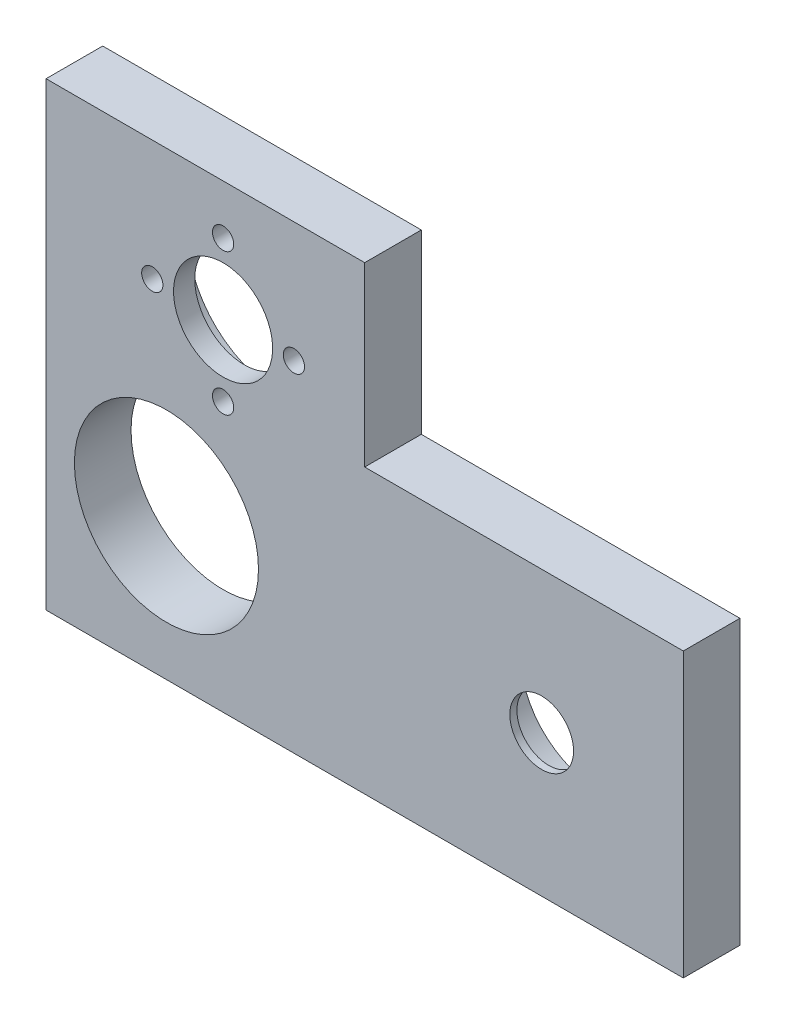
SolidWorks part; units mm, degrees
ref_plane "Front" through (0, 0, 0) normal (0, 0, 1) x (1, 0, 0)
ref_plane "Top" through (0, 0, 0) normal (0, 1, 0) x (1, 0, 0)
ref_plane "Right" through (0, 0, 0) normal (1, 0, 0) x (0, 0, -1)
sketch "Esquisse1" plane through (0, 0, 0) normal (0, 0, 1) x (1, 0, 0)
  line L1 (0, 0) -> (90, 0)
  line L2 (0, 0) -> (0, 65)
  line L3 (0, 65) -> (90, 65)
  line L4 (90, 0) -> (90, 65)
  circle A0 centre (70, 20) radius 4.5
  circle A1 centre (17, 20) radius 13
  circle A2 centre (25, 48) radius 13
  dimension "D3" = 9
  dimension "D4" = 20
  dimension "D6" = 53
  dimension "D8" = 26
  dimension "D9" = 26
  dimension "D1" = 90
  dimension "D2" = 65
  dimension "D5" = 70
  dimension "D7" = 20
  dimension "D10" = 53
  dimension "D11" = 48
extrude "Boss.-Extru.1" add sketch "Esquisse1" along normal blind 8
sketch "Esquisse2" plane through (0, 0, 0) normal (0, 0, -1) x (-1, 0, 0)
  circle A0 centre (-25, 48) radius 13
  circle A1 centre (-17, 20) radius 13 construction
  point P5 (0, 0)
  point P6 (-22.2507, 48)
extrude "Boss.-Extru.2" add sketch "Esquisse2" along normal blind 3 from surface starting at face at (45, 32.5, 8)
sketch "Esquisse3" plane through (0, 0, 5) normal (0, 0, -1) x (-1, 0, 0)
  line L0 (-15, 48) -> (-25, 48) construction
  circle A0 centre (-25, 48) radius 7
  circle A1 centre (-15, 48) radius 1.5
  circle A2 centre (-25, 38) radius 1.5
  circle A3 centre (-35, 48) radius 1.5
  circle A4 centre (-25, 58) radius 1.5
  point P5 (0, 0)
  point P6 (22.2507, 48)
  point P13 (-25, 48)
  dimension "D1" = 14
  dimension "D2" = 3
  dimension "D3" = 10
  dimension "D4" = 4
extrude "Enlèv. mat.-Extru.1" cut sketch "Esquisse3" against normal through all
sketch "Esquisse4" plane through (0, 0, 8) normal (0, 0, 1) x (1, 0, 0)
  circle A0 centre (70, 20) radius 11
  dimension "D1" = 22
extrude "Enlèv. mat.-Extru.2" cut sketch "Esquisse4" along normal blind 7 from surface starting at face at (30, 20, 0)
sketch "Esquisse5" plane through (0, 0, 0) normal (0, 0, -1) x (-1, 0, 0)
  line L1 (-90, 65) -> (-45, 65)
  line L2 (-90, 65) -> (-90, 40)
  line L3 (-90, 40) -> (-45, 40)
  line L4 (-45, 65) -> (-45, 40)
  dimension "D1" = 25
  dimension "D2" = 45
extrude "Enlèv. mat.-Extru.3" cut sketch "Esquisse5" against normal through all
